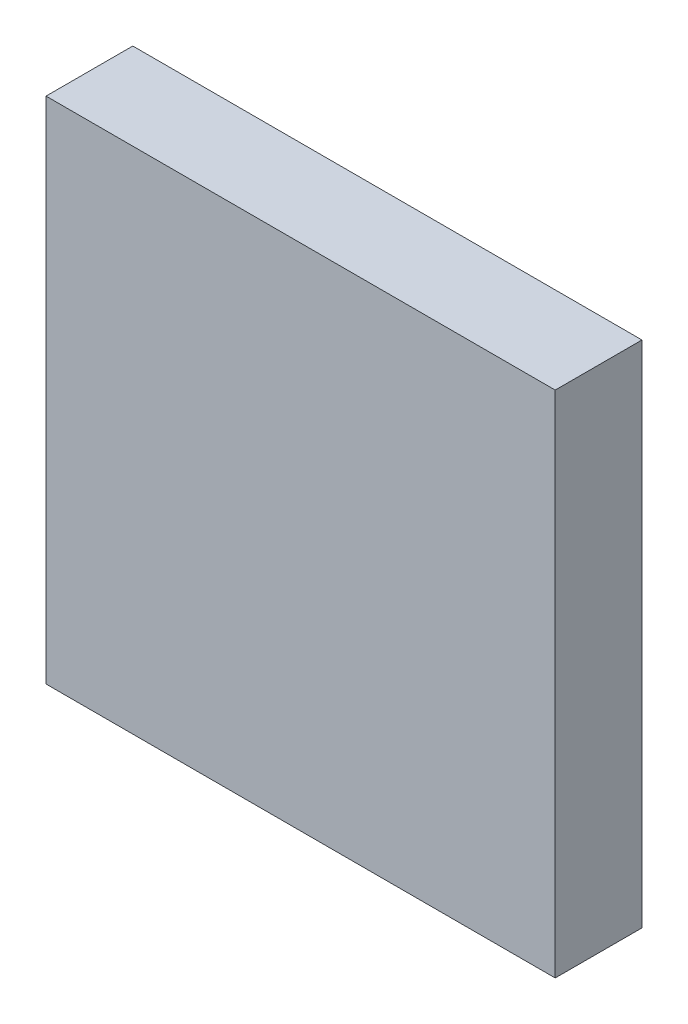
SolidWorks part; units mm, degrees
ref_plane "Ebene vorne" through (0, 0, 0) normal (0, 0, 1) x (1, 0, 0)
ref_plane "Ebene oben" through (0, 0, 0) normal (0, 1, 0) x (1, 0, 0)
ref_plane "Ebene rechts" through (0, 0, 0) normal (1, 0, 0) x (0, 0, -1)
sketch "Skizze1" plane through (0, 0, 0) normal (0, 0, 1) x (1, 0, 0)
  line L0 (67.5, 67.5) -> (-67.5, 67.5) construction
  line L1 (-67.5, 67.5) -> (-67.5, -67.5) construction
  line L2 (67.5, -67.5) -> (67.5, 67.5) construction
  line L3 (-67.5, -67.5) -> (67.5, -67.5) construction
  line L4 (67.5, 67.5) -> (-67.5, 67.5)
  line L5 (-67.5, 67.5) -> (-67.5, -67.5)
  line L6 (67.5, -67.5) -> (67.5, 67.5)
  line L7 (-67.5, -67.5) -> (67.5, -67.5)
  line L8 (65.5, 65.5) -> (-65.5, 65.5)
  line L9 (-65.5, 65.5) -> (-65.5, -65.5)
  line L10 (-65.5, -65.5) -> (65.5, -65.5)
  line L11 (65.5, -65.5) -> (65.5, 65.5)
  dimension "D1" = 2
extrude "Aufsatz-Linear austragen1" add sketch "Skizze1" along normal blind 18
sketch "Skizze2" plane through (0, 0, 18) normal (0, 0, 1) x (1, 0, 0)
  line L0 (-67.5, 67.5) -> (-67.5, -67.5) construction
  line L1 (-67.5, -67.5) -> (67.5, -67.5) construction
  line L2 (67.5, -67.5) -> (67.5, 67.5) construction
  line L3 (67.5, 67.5) -> (-67.5, 67.5) construction
  line L4 (-67.5, 67.5) -> (-67.5, -67.5)
  line L5 (-67.5, -67.5) -> (67.5, -67.5)
  line L6 (67.5, -67.5) -> (67.5, 67.5)
  line L7 (67.5, 67.5) -> (-67.5, 67.5)
extrude "Aufsatz-Linear austragen2" add sketch "Skizze2" along normal blind 5
extrude "Schnitt-Linear austragen1" cut sketch "Skizze3" against normal blind 11
sketch "Skizze3" plane through (-67.5, 0, 0) normal (-1, 0, 0) x (0, 0, 1)
  line L3 (5, -33.149) -> (3, -33.149)
  line L4 (3, -33.149) -> (3, -41.849)
  line L5 (3, -41.849) -> (5, -41.849)
  line L6 (5, -33.149) -> (7.4, -33.149)
  line L8 (5, -41.849) -> (7.4, -41.849)
  line L9 (7.4, -41.849) -> (7.4, -33.149)
